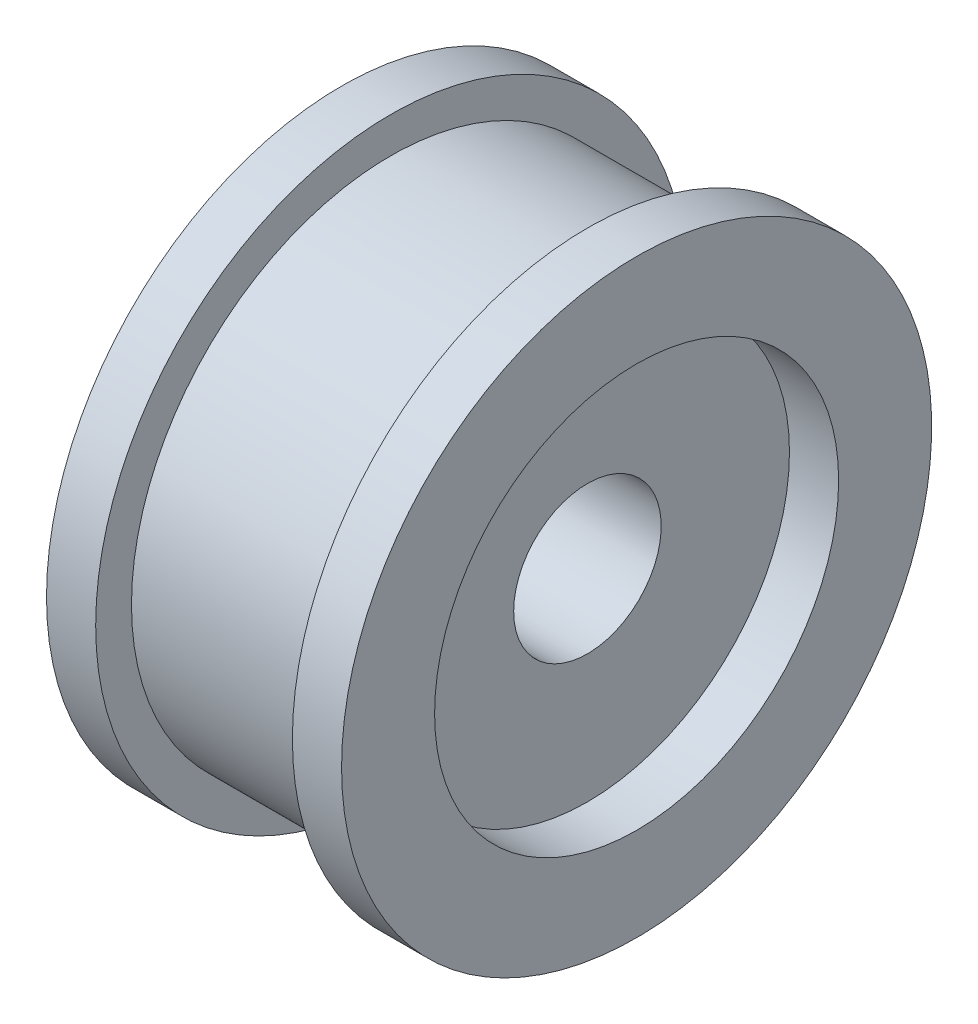
SolidWorks part; units mm, degrees
ref_plane "Front Plane" through (0, 0, 0) normal (0, 0, 1) x (1, 0, 0)
ref_plane "Top Plane" through (0, 0, 0) normal (0, 1, 0) x (1, 0, 0)
ref_plane "Right Plane" through (0, 0, 0) normal (1, 0, 0) x (0, 0, -1)
sketch "Sketch1" plane through (0, 0, 0) normal (0, 1, 0) x (1, 0, 0)
  line L0 (-2, 1.5) -> (2, 1.5)
  line L1 (-3, 6) -> (-2, 6)
  line L2 (-3, 6) -> (-3, 4.1081)
  line L4 (3, 6) -> (3, 4.1081)
  line L5 (2, 6) -> (3, 6)
  line L6 (-9.5251, 0) -> (9.5251, 0) construction
  line L8 (-2, 6) -> (-2, 5.272)
  line L9 (-2, 5.272) -> (2, 5.272)
  line L10 (2, 6) -> (2, 5.272)
  line L11 (-2, 4.1081) -> (-3, 4.1081)
  line L13 (-2, 4.1081) -> (-2, 1.5)
  line L15 (2, 4.1081) -> (2, 1.5)
  line L17 (2, 4.1081) -> (3, 4.1081)
  point P0 (0, 0)
  point P1 (0, 5.2009)
  point P6 (0, 10)
  point P12 (0, -10)
  point P14 (0, 0)
  point P16 (0, 5.272)
  dimension "D1" = 6
  dimension "D2" = 1
  dimension "D3" = 1
  dimension "D4" = 6
  dimension "D5" = 1.5
revolve "Revolve1" add sketch "Sketch1" angle 360 about L6
